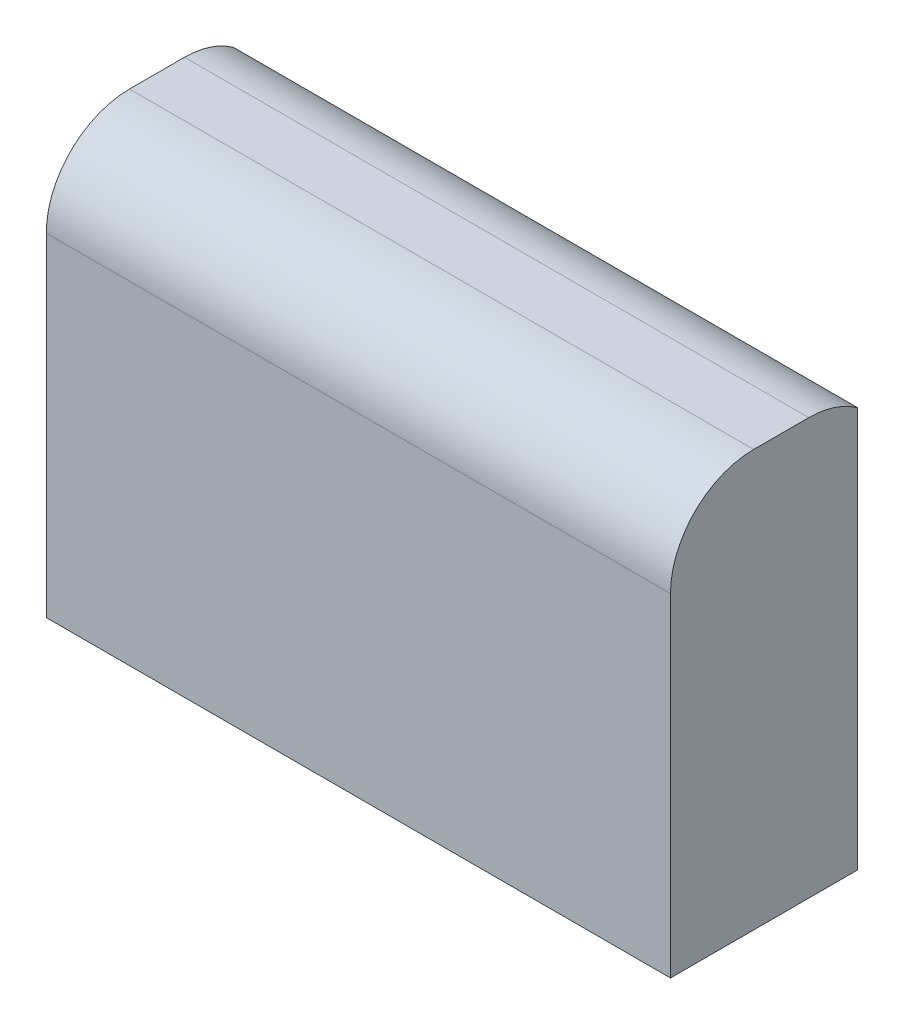
SolidWorks part; units mm, degrees
ref_plane "xy_plane" through (0, 0, 0) normal (0, 0, 1) x (1, 0, 0)
ref_plane "zx_plane" through (0, 0, 0) normal (0, 1, 0) x (1, 0, 0)
ref_plane "yz_plane" through (0, 0, 0) normal (1, 0, 0) x (0, 0, -1)
ref_axis "x_axis" through (-80.9, 0, 0) along (1, 0, 0)
ref_axis "y_axis" through (0, -50, 0) along (0, 1, 0)
ref_axis "z_axis" through (0, 0, -80.9) along (0, 0, 1)
ref_plane "xMid_plane" through (0, 0, 0) normal (1, 0, 0) x (0, 0, -1)
ref_plane "xMin_plane" through (-15, 0, 0) normal (1, 0, 0) x (0, 0, -1)
ref_plane "xMax_plane" through (15, 0, 0) normal (1, 0, 0) x (0, 0, -1)
ref_plane "yMid_plane" through (0, 0, 0) normal (0, 1, 0) x (1, 0, 0)
ref_plane "yMin_plane" through (0, -10, 0) normal (0, 1, 0) x (1, 0, 0)
ref_plane "yMax_plane" through (0, 10, 0) normal (0, 1, 0) x (1, 0, 0)
ref_plane "zMid_plane" through (0, 0, 0) normal (0, 0, 1) x (1, 0, 0)
ref_plane "zMin_plane" through (0, 0, -4.5) normal (0, 0, 1) x (1, 0, 0)
ref_plane "zMax_plane" through (0, 0, 4.5) normal (0, 0, 1) x (1, 0, 0)
sketch "projectionX_sketch" plane through (0, 0, 0) normal (1, 0, 0) x (0, 0, -1)
  line L0 (55, 10) -> (-55, 10) construction
  line L1 (-0.5, 10) -> (2.1457, 10)
  line L2 (-4.5, 6) -> (-4.5, -10)
  line L3 (-4.5, -10) -> (4.5, -10)
  line L4 (4.5, 9.2338) -> (4.5, -10)
  line L5 (55, -10) -> (-55, -10) construction
  line L7 (2.1457, 6) -> (4.5, 9.2338) construction
  line L8 (4.5, 55) -> (4.5, -55) construction
  line L9 (-4.5, 55) -> (-4.5, -55) construction
  line L10 (0, -50) -> (0, 50) construction
  arc A0 (-0.5, 10) -> (-4.5, 6) centre (-0.5, 6) ccw
  arc A1 (2.1457, 10) -> (4.5, 9.2338) centre (2.1457, 6) cw
  dimension "D1" = 4
  dimension "D2" = 36.055
extrude "mainBody_extrude" add sketch "projectionX_sketch" along normal up to surface (15 mm away) from surface up to plane "xMax_plane" starting at plane "xMin_plane"
ref_plane "pivotTargetZ_plane" through (0, 0, -4.5) normal (0, 0, 1) x (1, 0, 0)
equation "\"D1@xMin_plane\"= \"externalParameters.this.extentX\" / 2"
equation "\"D1@xMax_plane\" = \"externalParameters.this.extentX\" / 2"
equation "\"D1@yMin_plane\" = \"externalParameters.this.extentY\" / 2"
equation "\"D1@yMax_plane\" = \"externalParameters.this.extentY\" / 2"
equation "\"D1@zMin_plane\" = \"externalParameters.this.extentZ\" / 2"
equation "\"D1@zMax_plane\" = \"externalParameters.this.extentZ\" / 2"
